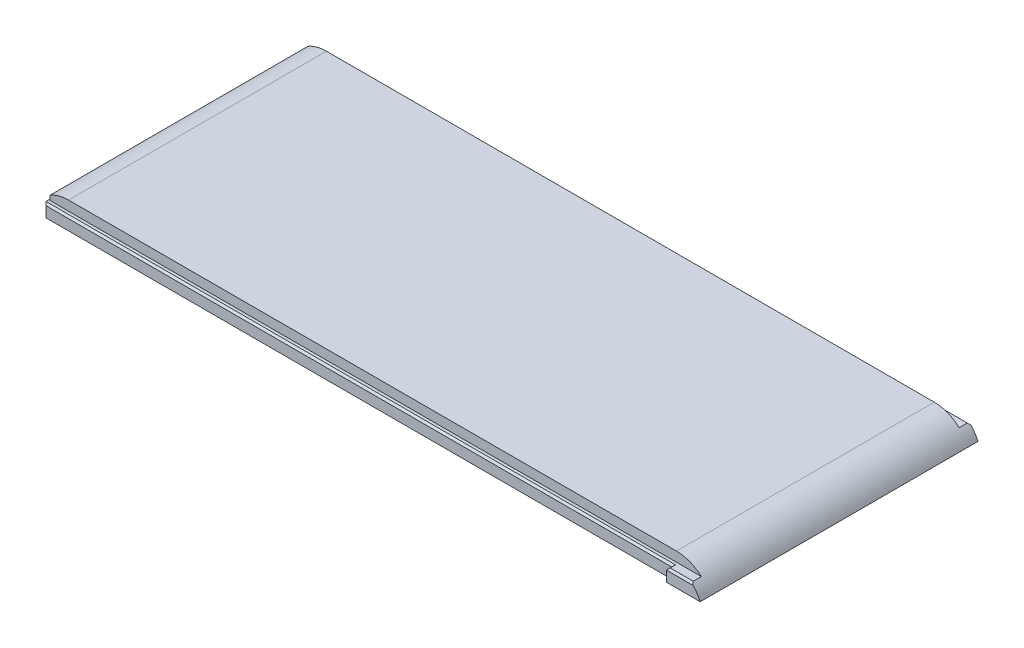
SolidWorks part; units mm, degrees
ref_plane "前视基准面" through (0, 0, 0) normal (0, 0, 1) x (1, 0, 0)
ref_plane "上视基准面" through (0, 0, 0) normal (0, 1, 0) x (1, 0, 0)
ref_plane "右视基准面" through (0, 0, 0) normal (1, 0, 0) x (0, 0, -1)
sketch "草图2" plane through (0, 0, 0) normal (0, 1, 0) x (1, 0, 0)
  line L1 (-31.0872, 15.1404) -> (42.9128, 15.1404)
  line L2 (-31.0872, 15.1404) -> (-31.0872, -12.8596)
  line L3 (-31.0872, -12.8596) -> (42.9128, -12.8596)
  line L4 (42.9128, 15.1404) -> (42.9128, -12.8596)
  dimension "D1" = 74
  dimension "D2" = 28
extrude "凸台-拉伸1" add sketch "草图2" along normal blind 4
fillet "圆角1" radius 4 2 edges at (-31.0872, 4, -1.1404) (42.9128, 4, -1.1404)
sketch "草图3" plane through (0, 0, -15.1404) normal (0, 0, -1) x (-1, 0, 0)
  line L1 (31.0872, 0) -> (-42.9128, 0)
  line L2 (31.0872, 0) -> (31.0872, 1.6)
  line L3 (31.0872, 1.6) -> (-42.9128, 1.6)
  line L4 (-42.9128, 0) -> (-42.9128, 1.6)
  line L5 (31.0872, 0) -> (31.0872, -28) construction
  point P5 (0, 0)
  dimension "D1" = 1.6
extrude "切除-拉伸1" cut sketch "草图3" against normal through all
sketch "草图4" plane through (0, 0, 12.8596) normal (0, 0, 1) x (1, 0, 0)
  line L0 (-31.0872, 0) -> (-31.0872, -28) construction
  line L1 (-31.0872, -1.1213) -> (-29.0872, -1.1213)
  line L2 (-31.0872, -1.1213) -> (-31.0872, 6.7558)
  line L3 (-31.0872, 6.7558) -> (-29.0872, 6.7558)
  line L4 (-29.0872, -1.1213) -> (-29.0872, 6.7558)
  dimension "D1" = 2
extrude "切除-拉伸2" cut sketch "草图4" against normal through all
sketch "草图5" plane through (0, 0, 12.8596) normal (0, 0, 1) x (1, 0, 0)
  line L0 (-29.0872, 1.6) -> (42.5789, 1.6) construction
  line L1 (38.9128, 1.6) -> (-29.0872, 1.6)
  line L2 (38.9128, 1.6) -> (38.9128, 2.95)
  line L3 (38.9128, 2.95) -> (-29.0872, 2.95)
  line L4 (-29.0872, 1.6) -> (-29.0872, 2.95)
  line L5 (38.9128, 1.6) -> (38.9128, 3) construction
  line L6 (-29.0872, 1.6) -> (-29.0872, 3.4641) construction
  dimension "D1" = 1.35
extrude "凸台-拉伸2" add sketch "草图5" along normal blind 0.5
sketch "草图6" plane through (0, 0, -15.1404) normal (0, 0, -1) x (-1, 0, 0)
  line L4 (-38.9128, 2.95) -> (-38.9128, 1.6)
  line L5 (29.0872, 2.95) -> (-38.9128, 2.95)
  line L6 (29.0872, 1.6) -> (29.0872, 2.95)
  line L7 (-38.9128, 1.6) -> (29.0872, 1.6)
  line L8 (-38.9128, 2.95) -> (-38.9128, 1.6)
  line L9 (29.0872, 2.95) -> (-38.9128, 2.95)
  line L10 (29.0872, 1.6) -> (29.0872, 2.95)
  line L11 (-38.9128, 1.6) -> (29.0872, 1.6)
  dimension "D1" = 0
extrude "凸台-拉伸3" add sketch "草图6" along normal blind 0.5
sketch "草图7" plane through (-29.0872, 0, 0) normal (-1, 0, 0) x (0, 0, 1)
  line L1 (13.3596, 2.95) -> (-15.6404, 2.95)
  line L2 (13.3596, 2.95) -> (13.3596, 1.6)
  line L3 (13.3596, 1.6) -> (-15.6404, 1.6)
  line L4 (-15.6404, 2.95) -> (-15.6404, 1.6)
extrude "凸台-拉伸4" add sketch "草图7" along normal blind 0.15
sketch "草图10" plane through (0, 0, -15.1404) normal (0, 0, -1) x (-1, 0, 0)
  line L0 (-38.9128, 2.95) -> (-42.3685, 2.95) construction
  line L1 (-42.5789, 1.6) -> (-38.9128, 1.6)
  line L2 (-38.9128, 1.6) -> (-38.9128, 2.95)
  line L3 (-38.9128, 2.95) -> (-41.6142, 2.95)
  arc A0 (-42.5789, 1.6) -> (-41.6142, 2.95) centre (-38.9128, 0) cw
extrude "凸台-拉伸5" add sketch "草图10" along normal blind 1.08
sketch "草图11" plane through (0, 0, 12.8596) normal (0, 0, 1) x (1, 0, 0)
  line L3 (38.9128, 1.6) -> (42.5789, 1.6)
  line L4 (38.9128, 2.95) -> (38.9128, 1.6)
  line L5 (41.6142, 2.95) -> (38.9128, 2.95)
  line L6 (38.9128, 1.6) -> (42.5789, 1.6)
  line L7 (38.9128, 2.95) -> (38.9128, 1.6)
  line L8 (41.6142, 2.95) -> (38.9128, 2.95)
  arc A1 (42.5789, 1.6) -> (41.6142, 2.95) centre (38.9128, 0) ccw
  arc A2 (42.5789, 1.6) -> (41.6142, 2.95) centre (38.9128, 0) ccw
  dimension "D1" = 0
extrude "凸台-拉伸6" add sketch "草图11" along normal blind 1.08
chamfer "倒角1" distance 0.2 angle 45 9 edges at (40.2635, 2.95, -16.2204) (40.2635, 2.95, 13.9396) (4.8378, 2.95, -15.6404) (-29.2372, 2.275, -15.6404) (-29.2372, 1.6, -1.1404) (-29.2372, 2.275, 13.3596) (4.8378, 2.95, 13.3596) (38.9128, 2.95, -15.9304) (38.9128, 2.95, 13.6496)
